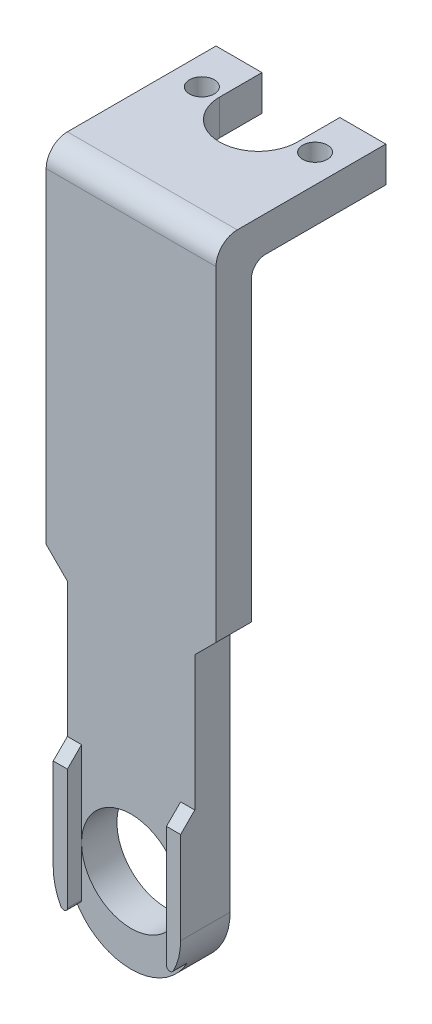
SolidWorks part; units mm, degrees
material "PMMA"
ref_plane "Front Plane" through (0, 0, 0) normal (0, 0, 1) x (1, 0, 0)
ref_plane "Top Plane" through (0, 0, 0) normal (0, 1, 0) x (1, 0, 0)
ref_plane "Right Plane" through (0, 0, 0) normal (1, 0, 0) x (0, 0, -1)
sketch "Sketch1" plane through (0, 0, 0) normal (0, 1, 0) x (1, 0, 0)
  line L1 (-12, 8) -> (-12, -18)
  line L2 (-12, -18) -> (12, -18)
  line L3 (12, -18) -> (12, 5.5)
  line L5 (-12, 8) -> (0, 8)
  line L6 (0, 8) -> (12, 8)
  line L7 (12, 8) -> (12, 5.5)
  line L8 (0, 8) -> (0, 0) construction
  line L9 (-17.0927, 0) -> (16.2972, 0) construction
  line L10 (0, 12.4942) -> (0, -10.971) construction
  line L11 (-8, 12.4942) -> (-8, -10.971) construction
  line L12 (8, 12.4942) -> (8, -10.971) construction
  circle A0 centre (0, 0) radius 5.5
  circle A1 centre (-8, 0) radius 1.75
  circle A2 centre (8, 0) radius 1.75
  dimension "D1" = 11
  dimension "D8" = 3.5
  dimension "D9" = 3.5
  dimension "D2" = 8
  dimension "D3" = 12
  dimension "D4" = 18
  dimension "D5" = 12
  dimension "D6" = 8
  dimension "D7" = 8
extrude "Boss-Extrude2" add sketch "Sketch1" along normal blind 5
sketch "Sketch2" plane through (0, 0, 0) normal (0, -1, 0) x (1, 0, 0)
  line L0 (-12, 18) -> (-12, 13)
  line L1 (-12, -8) -> (-12, 18) construction
  line L2 (-12, 13) -> (12, 13)
  line L3 (12, 18) -> (12, -8) construction
  line L4 (12, 13) -> (12, 18)
  line L5 (12, 18) -> (-12, 18)
  dimension "D1" = 5
extrude "Boss-Extrude3" add sketch "Sketch2" along normal blind 90
fillet "Fillet1" radius 3 1 edges at (0, 5, 18)
fillet "Fillet2" radius 2 1 edges at (0, 0, 13)
sketch "Sketch3" plane through (0, 0, 18) normal (0, 0, 1) x (1, 0, 0)
  line L0 (12, -90) -> (-12, -90) construction
  line L1 (0, 9.239) -> (0, -63.1826) construction
  circle A0 centre (0, -78) radius 7
  dimension "D1" = 14
  dimension "D2" = 12
extrude "Cut-Extrude1" cut sketch "Sketch3" against normal blind 60
sketch "Sketch4" plane through (0, 5, 0) normal (0, 1, 0) x (1, 0, 0)
  line L0 (-12, 8) -> (12, 8)
  line L1 (12, 8) -> (12, 6)
  line L2 (12, -15) -> (12, 8) construction
  line L3 (12, 6) -> (-12, 6)
  line L4 (-12, 8) -> (-12, -15) construction
  line L5 (-12, 6) -> (-12, 8)
  dimension "D1" = 2
extrude "Cut-Extrude2" cut sketch "Sketch4" against normal through all
sketch "Sketch5" plane through (0, 5, 0) normal (0, 1, 0) x (1, 0, 0)
  line L0 (-5.5, 0) -> (5.5, 0)
  line L1 (5.5, 0) -> (5.5, 6)
  line L2 (-12, 6) -> (12, 6) construction
  line L3 (5.5, 6) -> (-5.5, 6)
  line L4 (-5.5, 6) -> (-5.5, 0)
  circle A0 centre (0, 0) radius 5.5 construction
extrude "Cut-Extrude3" cut sketch "Sketch5" against normal through all
sketch "Sketch6" plane through (0, 0, 18) normal (0, 0, 1) x (1, 0, 0)
  line L0 (-12, -44) -> (-9, -47)
  line L1 (-12, 2) -> (-12, -90) construction
  line L2 (-9, -47) -> (-9, -90)
  line L3 (12, -90) -> (-12, -90) construction
  line L4 (-9, -90) -> (-12, -90)
  line L5 (-12, -90) -> (-12, -44)
  line L6 (0, 0) -> (0, -91.1725) construction
  line L7 (9, -90) -> (12, -90)
  line L8 (9, -47) -> (9, -90)
  line L9 (12, -44) -> (9, -47)
  line L10 (12, -90) -> (12, -44)
  dimension "D1" = 3
  dimension "D2" = 45
extrude "Cut-Extrude4" cut sketch "Sketch6" against normal through all
fillet "Fillet4" radius 9 2 edges at (9, -90, 15.5) (-9, -90, 15.5)
sketch "Sketch7" plane through (0, 0, 18) normal (0, 0, 1) x (1, 0, 0)
  line L0 (-7, -68) -> (-7, -86.6569)
  line L1 (-7, -68) -> (-9, -68)
  line L2 (-9, -81) -> (-9, -47) construction
  line L3 (-9, -68) -> (-9, -81)
  line L4 (0, -78) -> (-11.806, -78) construction
  line L5 (0, -59.1292) -> (0, -81.9536) construction
  line L6 (7, -68) -> (9, -68)
  line L7 (9, -68) -> (9, -81)
  line L8 (7, -68) -> (7, -86.6569)
  arc A0 (-9, -81) -> (-7, -86.6569) centre (0, -81) ccw
  arc A1 (9, -81) -> (7, -86.6569) centre (0, -81) cw
  dimension "D3" = 9
  dimension "D1" = 10
  dimension "D2" = 2
extrude "Boss-Extrude4" add sketch "Sketch7" along normal blind 2
chamfer "Chamfer1" distance 2 angle 45 2 edges at (8, -68, 18) (-8, -68, 18)
fillet "Fillet5" radius 0.5 2 edges at (7, -86.6569, 19) (-7, -86.6569, 19)
